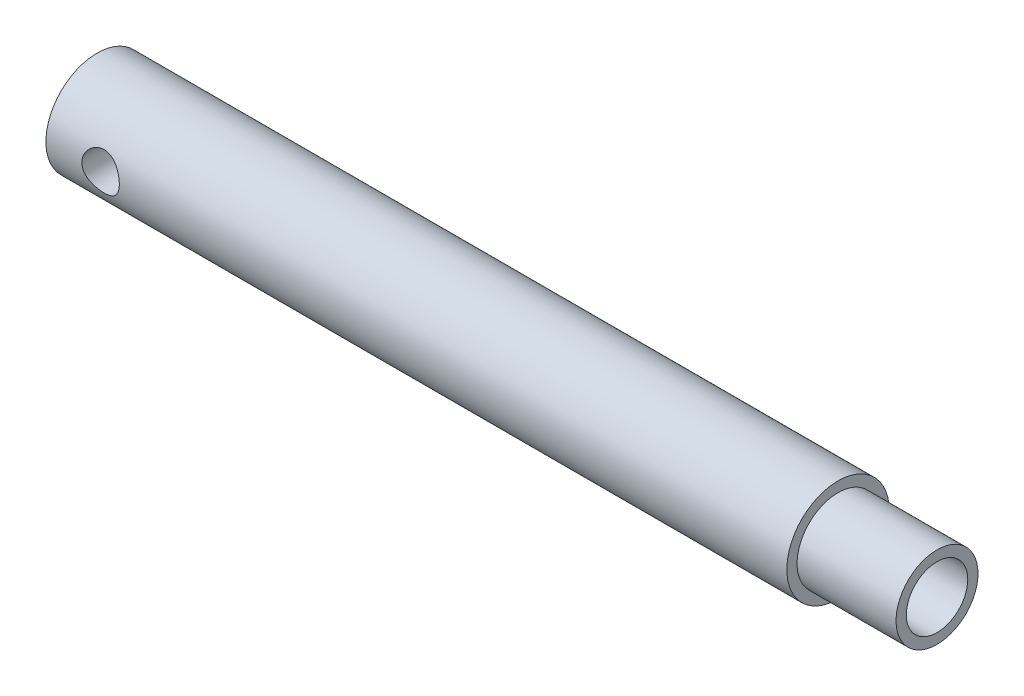
SolidWorks part; units mm, degrees
material "AISI 1020"
ref_plane "Plano frontal" through (0, 0, 0) normal (0, 0, 1) x (1, 0, 0)
ref_plane "Plano superior" through (0, 0, 0) normal (0, 1, 0) x (1, 0, 0)
ref_plane "Plano direito" through (0, 0, 0) normal (1, 0, 0) x (0, 0, -1)
sketch "Esboço1" plane through (0, 0, 0) normal (0, 0, 1) x (1, 0, 0)
  line L0 (0, 3.5) -> (0, 7.5)
  line L1 (0, 7.5) -> (108.5, 7.5)
  line L2 (108.5, 7.5) -> (108.5, 6)
  line L3 (108.5, 6) -> (123, 6)
  line L4 (123, 6) -> (123, 4.5)
  line L5 (123, 0) -> (0, 0) construction
  line L6 (0, 3.5) -> (11, 3.5)
  line L7 (100, 4) -> (11, 4)
  line L8 (11, 4) -> (11, 3.5)
  line L12 (123, 4.5) -> (100, 4.5)
  line L13 (100, 4) -> (100, 4.5)
  dimension "D4" = 4
  dimension "D1" = 108.5
  dimension "D2" = 7.5
  dimension "D3" = 12
  dimension "D5" = 8
  dimension "D6" = 14.5
  dimension "D7" = 11
  dimension "D8" = 23
  dimension "D9" = 9
revolve "Revolução1" add sketch "Esboço1" angle 360 about L5
cosmetic thread "Representação de rosca1" parameters "D2"=10.072
sketch "Esboço3" plane through (123, 0, 0) normal (1, 0, 0) x (0, 0, -1)
  circle A0 centre (0, 0) radius 5.75
  dimension "D1" = 11.5
curve "Hélice/Espiral1" pitch 1.5 height 13.875 turns 9.25
sketch "Esboço4" plane through (0, 0, 0) normal (0, 0, 1) x (1, 0, 0)
  line L0 (123, 6) -> (124.45, 6)
  line L1 (124.45, 6) -> (123.725, 5.25)
  line L2 (123.725, 5.25) -> (123, 6)
  line L3 (123.725, 6) -> (123.725, 5.25) construction
  dimension "D1" = 1.45
  dimension "D2" = 0.75
sweep "Varredura de corte1" [suppressed] cut profiles "Esboço4" path "Hélice/Espiral1"
sketch "Esboço5" plane through (0, 0, 0) normal (0, 1, 0) x (1, 0, 0)
  line L0 (0, 7.5) -> (0, -7.5) construction
  line L1 (8, 9) -> (8, 4)
  arc A0 (8, 9) -> (8, 4) centre (8, 6.5) ccw
  dimension "D1" = 5
  dimension "D3" = 8
  dimension "D2" = 6.5
revolve "Corte-Revolução1" [suppressed] cut sketch "Esboço5" angle 360 about L1
pattern_circular "PadrãoCircular1" [suppressed] count 2 over 360 of bodies 103
ref_plane "Plano1" through (0, 0, -7.5) normal (0, 0, -1) x (-1, 0, 0)
hole_wizard "Furo de diâmetro Ø5.5 (5.5)1" positions "Esboço6" profile "Esboço7" hole size "Ø5.5" standard "ISO" end condition up to next
sketch "Esboço6" plane through (0, 0, -7.5) normal (0, 0, -1) x (-1, 0, 0)
  line L0 (0, -7.5) -> (0, 7.5) construction
  point P0 (-8, 0)
  dimension "D1" = 8
sketch "Esboço7" plane through (8, 0, -7.5) normal (1, 0, 0) x (0, 1, 0)
  line L0 (0, 0) -> (0, 15)
  line L1 (0, 15) -> (2.75, 15)
  line L2 (2.75, 15) -> (2.75, 0)
  line L5 (2.75, 0) -> (0, 0)
  line L11 (0, -6.35) -> (0, 107.95) construction
  dimension "Thru Hole Dia." = 5.5
  dimension "Thru Hole Depth" = 15
mirror "Espelhar1" about plane through (0, 0, 0) normal (0, 0, 1) of "Furo de diâmetro Ø5.5 (5.5)1"
